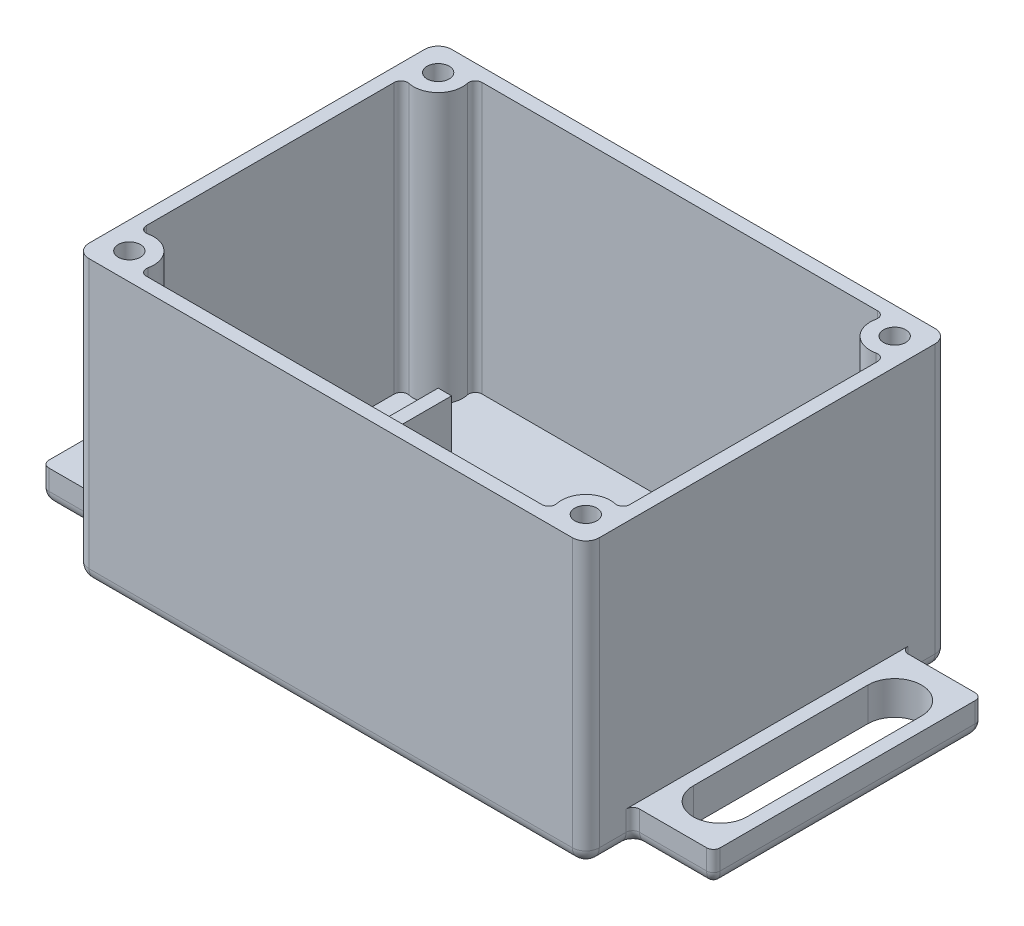
SolidWorks part; units mm, degrees
ref_plane "Piano frontale" through (0, 0, 0) normal (0, 0, 1) x (1, 0, 0)
ref_plane "Piano superiore" through (0, 0, 0) normal (0, 1, 0) x (1, 0, 0)
ref_plane "Piano destro" through (0, 0, 0) normal (1, 0, 0) x (0, 0, -1)
sketch "Schizzo1" plane through (0, 0, 0) normal (0, 1, 0) x (1, 0, 0)
  line L1 (-38, 27) -> (38, 27)
  line L2 (-38, 27) -> (-38, -27)
  line L3 (-38, -27) -> (38, -27)
  line L4 (38, 27) -> (38, -27)
  line L5 (-38, 27) -> (38, -27) construction
  line L6 (-38, -27) -> (38, 27) construction
  point P0 (0, 0)
  dimension "D1" = 76
  dimension "D2" = 54
extrude "Estrusione-Estrusione1" add sketch "Schizzo1" along normal blind 42
sketch "Schizzo2" plane through (0, 42, 0) normal (0, 1, 0) x (1, 0, 0)
  line L0 (38, 27) -> (-38, 27) construction
  line L1 (-36, 25) -> (36, 25)
  line L2 (-36, 25) -> (-36, -25)
  line L3 (-36, -25) -> (36, -25)
  line L4 (36, 25) -> (36, -25)
  line L5 (-36, 25) -> (36, -25) construction
  line L6 (-36, -25) -> (36, 25) construction
  line L8 (38, -27) -> (38, 27) construction
  point P0 (0, 0)
  dimension "D1" = 2
  dimension "D2" = 2
extrude "Taglio-Estrusione1" cut sketch "Schizzo2" against normal offset from surface (40.2 mm away) 1.8 up to face at (0, 0, 0)
sketch "Schizzo5" plane through (0, 1.8, 0) normal (0, 1, 0) x (1, 0, 0)
  line L2 (-46.9015, 0) -> (56.9538, 0) construction
  line L3 (0, 27.1281) -> (0, -29.0474) construction
  line L5 (38, 27) -> (-38, 27) construction
  line L6 (-38, 27) -> (-38, -27) construction
  line L7 (-36, 25) -> (-36, 19.9467)
  line L8 (-36, -25) -> (-36, 25) construction
  line L9 (-36, 25) -> (-30.9467, 25)
  line L10 (36, 25) -> (-36, 25) construction
  line L11 (36, 25) -> (30.9467, 25)
  line L12 (36, 25) -> (36, 19.9467)
  line L13 (36, -25) -> (36, -19.9467)
  line L14 (36, -25) -> (30.9467, -25)
  line L15 (-36, -25) -> (-36, -19.9467)
  line L16 (-36, -25) -> (-30.9467, -25)
  circle A0 centre (-34, 23) radius 1.65
  circle A1 centre (-34, 23) radius 3.65
  circle A3 centre (34, 23) radius 1.65
  circle A5 centre (34, 23) radius 3.65
  circle A6 centre (34, -23) radius 1.65
  circle A8 centre (34, -23) radius 3.65
  circle A9 centre (-34, -23) radius 3.65
  circle A10 centre (-34, -23) radius 1.65
  line M2 (36, -25) -> (36, 25)
  line M3 (36, 25) -> (-36, 25)
  line M4 (-36, 25) -> (-36, -25)
  line M5 (-36, -25) -> (36, -25)
  dimension "D1" = 3.3
  dimension "D4" = 2
  dimension "D2" = 4
  dimension "D3" = 4
extrude "Estrusione-Estrusione2" add sketch "Schizzo5" along normal through all contours A0 M3 M4 | A5 A3 M2 M3 | A8 A6 M2 M5 | A9 A10 M4 M5 region at (-33.4734, 1.8, -24.9201) region at (-32.3027, 1.8, 19.8592) region at (33.4734, 1.8, -24.9201) region at (31.4756, 1.8, 20.4756)
sketch "Schizzo6" plane through (0, 1.8, 0) normal (0, 1, 0) x (1, 0, 0)
  line L0 (-26, -23) -> (-26, 22)
  line L13 (-26, 22) -> (26, 22)
  line L14 (26, 22) -> (26, -23)
  line L15 (26, -23) -> (24, -23)
  line L16 (24, -23) -> (24, 20)
  line L17 (24, 20) -> (-24, 20)
  line L18 (-24, 20) -> (-24, -23)
  line L19 (-24, -23) -> (-26, -23)
  line L20 (0, 43.6943) -> (0, -44.2648) construction
  line L21 (38, 27) -> (-38, 27) construction
  circle A0 centre (-33, 13) radius 1.25
  circle A1 centre (-33, -13) radius 1.25
  circle A2 centre (33, -13) radius 1.25
  circle A3 centre (33, 13) radius 1.25
  point P8 (0, 20)
  dimension "D7" = 2.5
  dimension "D1" = 2
  dimension "D2" = 45
  dimension "D3" = 52
  dimension "D4" = 2
  dimension "D5" = 20
  dimension "D6" = 26
  dimension "D8" = 14
  dimension "D9" = 66
extrude "Taglio-Estrusione2" cut sketch "Schizzo6" against normal through all contours A0 | A3 | A2 | A1 region at (-33, 1.8, -13) region at (33, 1.8, 13) region at (33, 1.8, -13)
sketch "Schizzo7" plane through (0, 1.8, 0) normal (0, 1, 0) x (1, 0, 0)
  line L0 (0, 41.8493) -> (0, -45.2549) construction
  line L1 (-23.5, -12.5) -> (-23.5, 12.5)
  line L7 (-21.5, 12.5) -> (-21.5, -12.5)
  line L8 (-21.5, -12.5) -> (-23.5, -12.5)
  line L9 (-23.5, 12.5) -> (-21.5, 12.5)
  line L11 (23.5, -12.5) -> (23.5, 12.5)
  line L12 (21.5, -12.5) -> (23.5, -12.5)
  line L13 (21.5, 12.5) -> (21.5, -12.5)
  line L14 (23.5, 12.5) -> (21.5, 12.5)
  line L16 (-47.3098, 0) -> (47.7178, 0) construction
  point P13 (-23.5, 0)
  dimension "D1" = 25
  dimension "D2" = 21.5
  dimension "D5" = 2
extrude "Estrusione-Estrusione4" add sketch "Schizzo7" along normal blind 10
ref_plane "Piano1" through (0, 5, 0) normal (0, 1, 0) x (1, 0, 0)
sketch "Schizzo13" plane through (0, 0, 0) normal (0, -1, 0) x (1, 0, 0)
  line L0 (-38, -27) -> (-38, 27) construction
  line L1 (-50, 20) -> (-38, 20)
  line L2 (-50, 20) -> (-50, -20)
  line L3 (-50, -20) -> (-38, -20)
  line L4 (-38, 20) -> (-38, -20)
  line L5 (-50, 20) -> (-38, -20) construction
  line L6 (-50, -20) -> (-38, 20) construction
  line L7 (-44, 13) -> (-44, -13) construction
  line L8 (-40, 13) -> (-40, -13)
  line L9 (-48, 13) -> (-48, -13)
  line L10 (0, 24.5391) -> (0, -36.6296) construction
  line L11 (44, 13) -> (44, -13) construction
  line L12 (40, 13) -> (40, -13)
  line L13 (48, 13) -> (48, -13)
  line L14 (50, -20) -> (38, -20)
  line L15 (38, 20) -> (38, -20)
  line L16 (50, 20) -> (38, 20)
  line L17 (50, 20) -> (50, -20)
  arc A0 (-40, 13) -> (-48, 13) centre (-44, 13) ccw
  arc A1 (-48, -13) -> (-40, -13) centre (-44, -13) ccw
  arc A2 (40, 13) -> (48, 13) centre (44, 13) cw
  arc A3 (48, -13) -> (40, -13) centre (44, -13) cw
  point P0 (-44, 0)
  point P10 (-44, 0)
  point P19 (44, 0)
  dimension "D1" = 40
  dimension "D2" = 12
  dimension "D3" = 8
  dimension "D5" = 26
extrude "Estrusione-Estrusione5" add sketch "Schizzo13" against normal blind 5
fillet "Raccordo4" radius 1 8 edges at (-38, 2.5, -20) (-50, 2.5, -20) (-50, 2.5, 20) (-38, 2.5, 20) (38, 2.5, -20) (50, 2.5, -20) (38, 2.5, 20) (50, 2.5, 20)
fillet "Raccordo2" radius 2 24 edges at (38, 0, -24) (38, 0, 24) (0, 0, 27) (-38, 0, -24) (-38, 0, 24) (0, 0, -27) (38, 21, -27) (38, 21, 27) (-38, 21, 27) (-38, 21, -27) (-38.2929, 0, 20.2929) (-44, 0, 20) (-49.7071, 0, 19.7071) (-50, 0, 0) (-49.7071, 0, -19.7071) (-44, 0, -20) (-38.2929, 0, -20.2929) (38.2929, 0, -20.2929) (44, 0, -20) (49.7071, 0, -19.7071) (50, 0, 0) (49.7071, 0, 19.7071) (44, 0, 20) (38.2929, 0, 20.2929)
fillet "Raccordo3" radius 1 8 edges at (30.9467, 21.9, -25) (36, 21.9, -19.9467) (36, 21.9, 19.9467) (30.9467, 21.9, 25) (-30.9467, 21.9, 25) (-36, 21.9, 19.9467) (-36, 21.9, -19.9467) (-30.9467, 21.9, -25)
